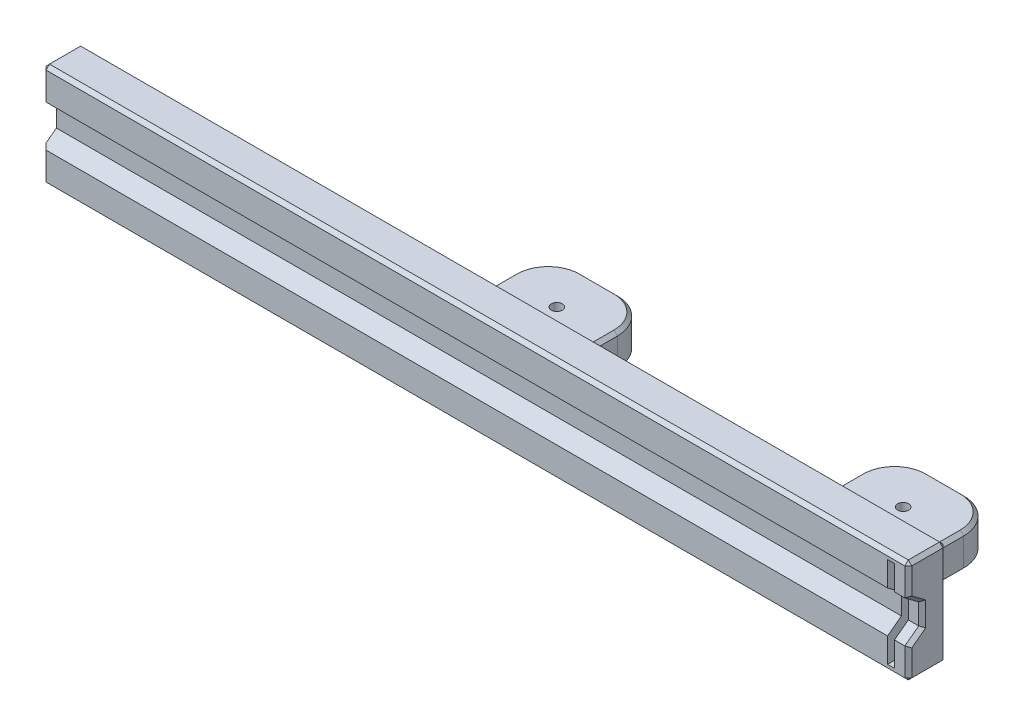
SolidWorks part; units mm, degrees
ref_plane "前基準面" through (0, 0, 0) normal (0, 0, 1) x (1, 0, 0)
ref_plane "上基準面" through (0, 0, 0) normal (0, 1, 0) x (1, 0, 0)
ref_plane "右基準面" through (0, 0, 0) normal (1, 0, 0) x (0, 0, -1)
sketch "草圖1" plane through (0, 0, 0) normal (0, 0, 1) x (1, 0, 0)
  line L0 (0, 0) -> (250, 0)
  line L1 (250, 0) -> (250, 30)
  line L2 (250, 30) -> (0, 30)
  line L3 (0, 30) -> (0, 0)
  dimension "D1" = 30
  dimension "D2" = 250
extrude "填料-伸長1" add sketch "草圖1" along normal blind 11
sketch "草圖4" plane through (0, 0, 0) normal (0, 0, -1) x (-1, 0, 0)
  line L0 (-250, 15) -> (0, 15)
  line L1 (-250, 0) -> (-250, 30) construction
  line L2 (0, 30) -> (0, 0) construction
  line L3 (-125, 30) -> (-125, 0)
  line L4 (-250, 30) -> (0, 30) construction
  line L5 (0, 0) -> (-250, 0) construction
  line L6 (-140, 15) -> (-125, 15)
  line L7 (-125, 15) -> (-110, 15)
  line L8 (-140, 15) -> (-140, 20)
  line L9 (-140, 20) -> (-110, 20)
  line L10 (-110, 20) -> (-110, 15)
  line L11 (-140, 15) -> (-140, 10)
  line L12 (-140, 10) -> (-125, 10)
  line L13 (-125, 10) -> (-110, 10)
  line L14 (-110, 10) -> (-110, 15)
  line L16 (-164.6389, 10) -> (-194.6389, 10)
  line L17 (-164.6389, 10) -> (-164.6389, 20)
  line L18 (-164.6389, 20) -> (-194.6389, 20)
  line L19 (-194.6389, 10) -> (-194.6389, 20)
  line L20 (-164.6389, 10) -> (-194.6389, 20) construction
  line L21 (-164.6389, 20) -> (-194.6389, 10) construction
  point P17 (-179.6389, 15)
  dimension "D1" = 15
  dimension "D2" = 15
  dimension "D3" = 5
  dimension "D4" = 5
  dimension "D5" = 10
  dimension "D6" = 30
extrude "填料-伸長2" add sketch "草圖4" along normal blind 25 contours L11 L12 L3 L0 | L9 L8 L0 L3 | L10 L9 L3 L0 | L13 L14 L0 L3 region at (132.5, 17.5, 0) region at (132.5, 12.5, 0) region at (117.5, 17.5, 0) region at (117.5, 12.5, 0)
sketch "草圖5" plane through (250, 0, 0) normal (1, 0, 0) x (0, 0, -1)
  line L0 (-11, 30) -> (-11, 21)
  line L1 (-11, 0) -> (-11, 30) construction
  line L2 (-7, 15) -> (-7, 12)
  line L3 (-7, 15) -> (-7, 18)
  line L4 (-7, 18) -> (-11, 21)
  line L5 (-11, 9) -> (-11, 0)
  line L6 (-11, 15) -> (0, 15)
  line L7 (0, 30) -> (0, 0) construction
  line L8 (-7, 12) -> (-11, 9)
  line L9 (-11, 9) -> (-11, 21)
  line M6 (-11, 30) -> (-11, 0)
  dimension "D1" = 12
  dimension "D2" = 30
  dimension "D3" = 6
  dimension "D4" = 3
  dimension "D5" = 3
  dimension "D6" = 4
extrude "除料-伸長2" cut sketch "草圖5" against normal through all contours L6 L3 L4 M6 | L8 L2 L6 M6 region at (250, 17.3333, 9.2222) region at (250, 12.6667, 9.2222)
sketch "草圖6" plane through (0, 10, 0) normal (0, -1, 0) x (1, 0, 0)
  line L0 (125, 0) -> (125, -25)
  line L1 (250, 0) -> (0, 0) construction
  line L2 (140, -25) -> (110, -25) construction
  line L3 (110, -12.5) -> (140, -12.5)
  line L4 (110, -25) -> (110, 0) construction
  line L5 (140, -25) -> (140, 0) construction
  circle A0 centre (125, -12.5) radius 1.6
  dimension "D1" = 3.2
extrude "除料-伸長3" cut sketch "草圖6" against normal through all contours L3 A0 L0 | L0 A0 L3 | L3 A0 L0 | L0 A0 L3 region at (125.6791, 10, -11.8209) region at (124.3209, 10, -11.8209) region at (125.6791, 10, -13.1791) region at (124.3209, 10, -13.1791)
sketch "草圖7" plane through (0, 10, 0) normal (0, -1, 0) x (1, 0, 0)
  line L0 (125, -14.1) -> (125, -25)
  line L1 (140, -25) -> (110, -25) construction
  circle A0 centre (125, -12.5) radius 1.6 construction
sketch "草圖9" plane through (0, 0, 0) normal (0, 0, -1) x (-1, 0, 0)
  line L1 (-194.6389, 20) -> (-164.6389, 20)
  line L2 (-194.6389, 20) -> (-194.6389, 10)
  line L3 (-194.6389, 10) -> (-164.6389, 10)
  line L4 (-164.6389, 20) -> (-164.6389, 10)
  line L5 (-194.6389, 20) -> (-164.6389, 10) construction
  line L6 (-194.6389, 10) -> (-164.6389, 20) construction
  point P0 (-179.6389, 15)
sketch "草圖11" plane through (0, 0, 0) normal (0, 0, -1) x (-1, 0, 0)
  line L0 (-125, 15) -> (-225, 15)
  line L1 (-250, 15) -> (0, 15) construction
  line L3 (-240, 10) -> (-210, 10)
  line L4 (-240, 10) -> (-240, 20)
  line L5 (-240, 20) -> (-210, 20)
  line L6 (-210, 10) -> (-210, 20)
  line L7 (-240, 10) -> (-210, 20) construction
  line L8 (-240, 20) -> (-210, 10) construction
  dimension "D1" = 100
  dimension "D2" = 10
  dimension "D3" = 30
extrude "填料-伸長4" add sketch "草圖11" along normal blind 25 contours L3 L6 L5 L4 region at (239.6838, 15, 0)
sketch "草圖12" plane through (0, 20, 0) normal (0, 1, 0) x (1, 0, 0)
  line L0 (240, 12.5) -> (210, 12.5)
  line L1 (240, 25) -> (240, 0) construction
  line L2 (210, 25) -> (210, 0) construction
  circle A0 centre (225, 12.5) radius 1.6
  dimension "D1" = 3.2
extrude "除料-伸長5" cut sketch "草圖12" against normal through all contours A0
fillet "圓角1" radius 10 4 edges at (110, 15, -25) (140, 15, -25) (210, 15, -25) (240, 15, -25)
sketch "草圖13" plane through (0, 0, 11) normal (0, 0, 1) x (1, 0, 0)
  line L1 (244, 28.1) -> (246, 28.1)
  line L2 (244, 28.1) -> (244, 1.9)
  line L3 (244, 1.9) -> (246, 1.9)
  line L4 (246, 28.1) -> (246, 1.9)
  line L5 (250, 15) -> (0, 15) construction
  line L6 (250, 0) -> (250, 30) construction
  dimension "D1" = 2
  dimension "D2" = 26.2
  dimension "D3" = 13.1
  dimension "D4" = 4
extrude "除料-伸長6" cut sketch "草圖13" against normal through all
chamfer "導角1" distance 1 angle 45 45 edges at (250, 15, 0) (250, 30, 5.5) (250, 0, 5.5) (125, 30, 11) (125, 0, 11) (0, 30, 5.5) (125, 30, 0) (125, 0, 0) (0, 15, 0) (0, 0, 5.5) (225, 10, -25) (225, 20, -25) (212.9289, 20, -22.0711) (212.9289, 10, -22.0711) (237.0711, 10, -22.0711) (237.0711, 20, -22.0711) (225, 20, 0) (210, 20, -7.5) (210, 15, 0) (210, 10, -7.5) (225, 10, 0) (240, 10, -7.5) (240, 15, 0) (240, 20, -7.5) (125, 20, -25) (125, 10, -25) (112.9289, 20, -22.0711) (112.9289, 10, -22.0711) (137.0711, 20, -22.0711) (137.0711, 10, -22.0711) (110, 20, -7.5) (125, 10, 0) (110, 10, -7.5) (110, 15, 0) (125, 20, 0) (140, 20, -7.5) (140, 15, 0) (140, 10, -7.5) (250, 4.5, 11) (250, 10.5, 9) (250, 15, 7) (250, 19.5, 9) (250, 25.5, 11) (0, 25.5, 11) (0, 4.5, 11)
